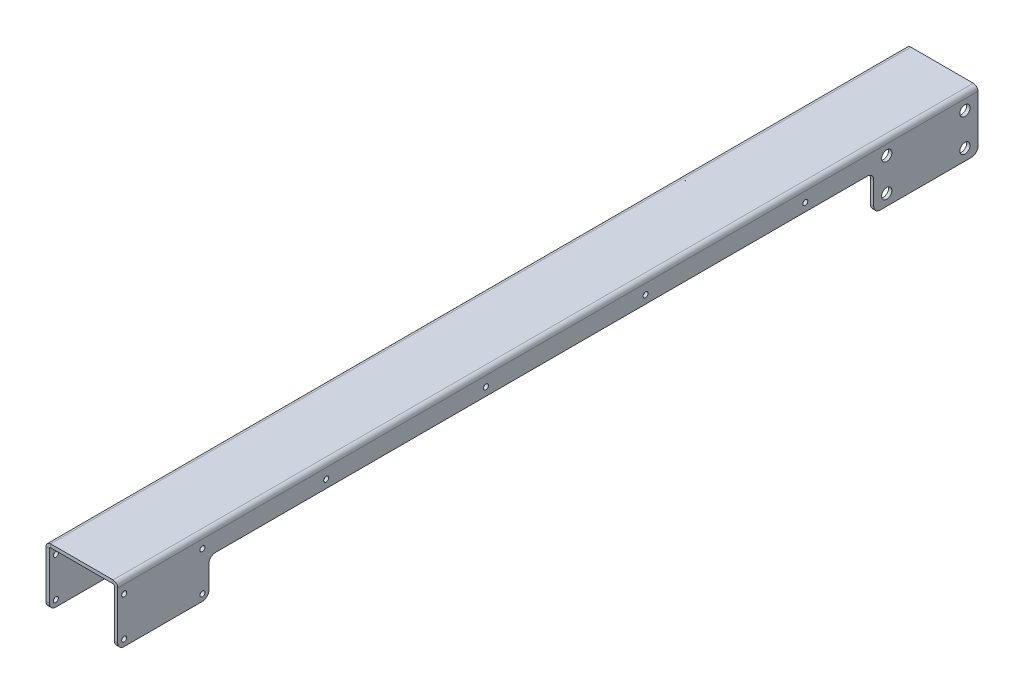
SolidWorks part; units mm, degrees
note: The reader was unsure of these and kept them because the rebuilt part matched: flange length of "Edge-Flange2".
material "5052-H32"
ref_plane "Front Plane" through (0, 0, 0) normal (0, 0, 1) x (1, 0, 0)
ref_plane "Top Plane" through (0, 0, 0) normal (0, 1, 0) x (1, 0, 0)
ref_plane "Right Plane" through (0, 0, 0) normal (1, 0, 0) x (0, 0, -1)
sketch "Sketch1" plane through (0, 0, 0) normal (0, 1, 0) x (1, 0, 0)
  line L1 (-34.925, 838.2) -> (34.925, 838.2)
  line L2 (-34.925, 838.2) -> (-34.925, 0)
  line L3 (-34.925, 0) -> (34.925, 0)
  line L4 (34.925, 838.2) -> (34.925, 0)
  point P4 (0, 0)
  dimension "D1" = 69.85
  dimension "D2" = 838.2
base flange "Base-Flange1" sketch "Sketch1" thickness 3.2639 reverse thickness direction no parameters "D1"=1.27
edge flange "Edge-Flange2" sketch "Sketch21" flange profiles "Sketch21", "Sketch22" flange angle 90 flange length 22.225 flange position material inside bend radius 1.27 thickness 3.2639 relief rectangular parameters "D6"=10, "D8"=1
sketch "Sketch21" plane through (34.925, -3.2639, 0) normal (-1, 0, 0) x (0, 0, -1)
  line L2 (0, 0) -> (0, 18.9611)
  line L3 (0, 18.9611) -> (838.2, 18.9611)
  line L4 (838.2, 18.9611) -> (838.2, 0)
  line L5 (838.2, 0) -> (0, 0) construction
  line L6 (838.2, 0) -> (0, 0)
sketch "Sketch22" plane through (-34.925, -3.2639, 0) normal (1, 0, 0) x (0, 0, 1)
  line L0 (0, 0) -> (-838.2, 0) construction
  line L1 (0, 0) -> (-838.2, 0)
  line L2 (0, 0) -> (0, 18.9611)
  line L3 (0, 18.9611) -> (-838.2, 18.9611)
  line L4 (-838.2, 18.9611) -> (-838.2, 0)
bend "EdgeBend2" bend radius 1.27 bend angle 90 parameters "D5"=1
bend "EdgeBend3" bend radius 1.27 bend angle 90 parameters "D5"=2
sketch "Sketch23" plane through (-34.925, 0, 0) normal (-1, 0, 0) x (0, 0, 1)
  line L0 (-838.2, 0) -> (0, 0) construction
  line L1 (-838.2, -22.225) -> (-736.6, -22.225)
  line L2 (-838.2, -22.225) -> (-838.2, -57.15)
  line L3 (-838.2, -57.15) -> (-736.6, -57.15)
  line L4 (-736.6, -22.225) -> (-736.6, -57.15)
  dimension "D1" = 101.6
  dimension "D2" = 57.15
extrude "Boss-Extrude1" add sketch "Sketch23" against normal up to surface (3.2639 mm away) up to face at (-31.6611, -13.3794, -419.1)
sketch "Sketch24" plane through (34.925, 0, 0) normal (1, 0, 0) x (0, 0, -1)
  line L4 (838.2, -22.225) -> (736.6, -22.225)
  line L5 (736.6, -22.225) -> (736.6, -57.15)
  line L6 (736.6, -57.15) -> (838.2, -57.15)
  line L7 (838.2, -57.15) -> (838.2, -22.225)
  line L8 (838.2, -22.225) -> (736.6, -22.225)
  line L9 (736.6, -22.225) -> (736.6, -57.15)
  line L10 (736.6, -57.15) -> (838.2, -57.15)
  line L11 (838.2, -57.15) -> (838.2, -22.225)
  dimension "D1" = 0
extrude "Boss-Extrude2" add sketch "Sketch24" against normal up to surface (3.2639 mm away) up to face at (31.6611, -13.3794, -419.1)
sketch "Sketch32" plane through (-34.925, 0, 0) normal (-1, 0, 0) x (0, 0, 1)
  line L0 (-838.2, -57.15) -> (-736.6, -57.15) construction
  line L1 (0, -22.225) -> (-88.9, -22.225)
  line L2 (0, -22.225) -> (0, -57.15)
  line L3 (0, -57.15) -> (-88.9, -57.15)
  line L4 (-88.9, -22.225) -> (-88.9, -57.15)
  dimension "D1" = 88.9
extrude "Boss-Extrude3" add sketch "Sketch32" against normal up to surface (3.2639 mm away)
sketch "Sketch33" plane through (34.925, 0, 0) normal (1, 0, 0) x (0, 0, -1)
  line L4 (88.9, -22.225) -> (0, -22.225)
  line L5 (88.9, -57.15) -> (88.9, -22.225)
  line L6 (0, -57.15) -> (88.9, -57.15)
  line L7 (0, -22.225) -> (0, -57.15)
  line L8 (88.9, -22.225) -> (0, -22.225)
  line L9 (88.9, -57.15) -> (88.9, -22.225)
  line L10 (0, -57.15) -> (88.9, -57.15)
  line L11 (0, -22.225) -> (0, -57.15)
  dimension "D1" = 0
extrude "Boss-Extrude4" add sketch "Sketch33" against normal up to surface (3.2639 mm away)
sketch "Sketch25" plane through (-34.925, 0, 0) normal (-1, 0, 0) x (0, 0, 1)
  line L0 (-838.2, 0) -> (0, 0) construction
  line L1 (0, -4.5339) -> (0, -57.15) construction
  point P0 (-203.2, -14.2875)
  dimension "D1" = 14.2875
  dimension "D2" = 203.2
hole_wizard "#10 (0.1935) Diameter Hole2" positions "Sketch26" profile "Sketch27" hole size "#10" standard "ANSI Inch" end condition through all
sketch "Sketch26" plane through (-34.925, 0, 0) normal (-1, 0, 0) x (0, 0, 1)
  point P0 (-203.2, -14.2875)
sketch "Sketch27" plane through (-34.925, -14.2875, -203.2) normal (0, 1, 0) x (0, 0, 1)
  line L0 (0, 0) -> (0, 69.85)
  line L1 (0, 69.85) -> (2.4574, 69.85)
  line L2 (2.4574, 69.85) -> (2.4574, 0)
  line L5 (2.4574, 0) -> (0, 0)
  line L11 (0, -6.35) -> (0, 107.95) construction
  dimension "Thru Hole Dia." = 4.9149
  dimension "Thru Hole Depth" = 69.85
pattern_linear "LPattern2" count 4 spacing 155.575 along (0, 0, -1) of "#10 (0.1935) Diameter Hole2"
sketch "Sketch29" plane through (-34.925, 0, 0) normal (-1, 0, 0) x (0, 0, 1)
  line L1 (-825.5, -14.4429) -> (-749.3, -14.4429)
  line L2 (-825.5, -14.4429) -> (-825.5, -46.1929)
  line L3 (-825.5, -46.1929) -> (-749.3, -46.1929)
  line L4 (-749.3, -14.4429) -> (-749.3, -46.1929)
  line L5 (0, -4.5339) -> (0, -57.15) construction
  line L6 (-838.2, -57.15) -> (-736.6, -57.15) construction
  dimension "D1" = 76.2
  dimension "D2" = 31.75
  dimension "D3" = 42.7071
  dimension "D4" = 749.3
hole_wizard "25/64 (0.39063) Diameter Hole1" positions "Sketch30" profile "Sketch31" hole size "25/64" standard "ANSI Inch" end condition through all
sketch "Sketch30" plane through (-34.925, 0, 0) normal (-1, 0, 0) x (0, 0, 1)
  point P0 (-825.5, -14.4429)
  point P3 (-825.5, -46.1929)
  point P6 (-749.3, -14.4429)
  point P9 (-749.3, -46.1929)
sketch "Sketch31" plane through (-34.925, -14.4429, -825.5) normal (0, 1, 0) x (0, 0, 1)
  line L0 (0, 0) -> (0, 69.85)
  line L1 (0, 69.85) -> (4.961, 69.85)
  line L2 (4.961, 69.85) -> (4.961, 0)
  line L5 (4.961, 0) -> (0, 0)
  line L11 (0, -6.35) -> (0, 107.95) construction
  dimension "Thru Hole Dia." = 9.922
  dimension "Thru Hole Depth" = 69.85
sketch "Sketch34" plane through (-34.925, 0, 0) normal (-1, 0, 0) x (0, 0, 1)
  line L0 (0, -4.5339) -> (0, -57.15) construction
  line L1 (-6.35, -12.7) -> (-82.55, -12.7)
  line L2 (-6.35, -12.7) -> (-6.35, -50.8)
  line L3 (-6.35, -50.8) -> (-82.55, -50.8)
  line L4 (-82.55, -12.7) -> (-82.55, -50.8)
  line L7 (-838.2, 0) -> (0, 0) construction
  dimension "D1" = 76.2
  dimension "D2" = 38.1
  dimension "D3" = 6.35
  dimension "D4" = 12.7
hole_wizard "#10 (0.1935) Diameter Hole3" positions "Sketch35" profile "Sketch36" hole size "#10" standard "ANSI Inch" end condition through all
sketch "Sketch35" plane through (-34.925, 0, 0) normal (-1, 0, 0) x (0, 0, 1)
  point P0 (-82.55, -12.7)
  point P3 (-82.55, -50.8)
  point P6 (-6.35, -12.7)
  point P9 (-6.35, -50.8)
sketch "Sketch36" plane through (-34.925, -12.7, -82.55) normal (0, 1, 0) x (0, 0, 1)
  line L0 (0, 0) -> (0, 69.85)
  line L1 (0, 69.85) -> (2.4574, 69.85)
  line L2 (2.4574, 69.85) -> (2.4574, 0)
  line L5 (2.4574, 0) -> (0, 0)
  line L11 (0, -6.35) -> (0, 107.95) construction
  dimension "Thru Hole Dia." = 4.9149
  dimension "Thru Hole Depth" = 69.85
fillet "Fillet2" radius 6.35 12 edges at (-33.2931, -22.225, -736.6) (33.293, -22.225, -736.6) (33.2931, -57.15, -736.6) (-33.2931, -57.15, -736.6) (-33.2931, -57.15, -838.2) (33.293, -57.15, -838.2) (33.2931, -57.15, -88.9) (-33.2931, -57.15, -88.9) (-33.2931, -22.225, -88.9) (33.2931, -22.225, -88.9) (33.2931, -57.15, 0) (-33.2931, -57.15, 0)
sketch "Bend-Lines1" [suppressed] plane through (0, 0, 0) normal (0, 1, 0) x (1, 0, 0)
sketch "Bounding-Box1" [suppressed] plane through (0, 0, 0) normal (0, 1, 0) x (1, 0, 0)
sheet metal parameters "Sheet-Metal1" thickness 3.2639 parameters "D1"=1.27
flat pattern "Flat-Pattern1" [suppressed]
sketch "Bend-Lines2" plane through (0, 0, 0) normal (0, 1, 0) x (1, 0, 0)
sketch3d "Bounding-Box2" [suppressed]
  line L0 (-34.925, 685.8, 0) -> (-34.925, 0, 0) construction
  line L1 (34.925, 685.8, 0) -> (34.925, 0, 0) construction
  line L2 (-34.925, 685.8, 0) -> (34.925, 685.8, 0) construction
  line L3 (-34.925, 0, 0) -> (34.925, 0, 0) construction
sketch "Sketch12-2" [suppressed] plane through (0, -3.2639, 0) normal (0, -1, 0) x (1, 0, 0)
  line L0 (-34.925, -866.8593) -> (34.925, -866.8593)
  line L1 (34.925, -685.8) -> (-34.925, -685.8) construction
  dimension "D1" = 181.0593
  dimension "D2" = 69.85
sheet metal parameters "Sheet-Metal20" thickness 3.2639 parameters "D1"=1.27
flat pattern "Flat-Pattern1"
sketch "Bend-Lines2" plane through (0, 0, 0) normal (0, 1, 0) x (1, 0, 0)
  line L0 (-32.6703, 863.6) -> (-32.6703, 0) construction
  line L1 (32.6703, 0) -> (32.6703, 863.6) construction
  line L2 (-32.6703, 863.6) -> (-32.6703, 0) construction
  line L3 (32.6703, 0) -> (32.6703, 863.6) construction
sketch3d "Bounding-Box2" [suppressed]
  line L0 (-52.6406, 863.6, 0) -> (-52.6406, 0, 0) construction
  line L1 (52.6406, 863.6, 0) -> (52.6406, 0, 0) construction
  line L2 (-52.6406, 863.6, 0) -> (52.6406, 863.6, 0) construction
  line L3 (-52.6406, 0, 0) -> (52.6406, 0, 0) construction
bend of the flat pattern "Flatten-<EdgeBend2>1"
bend of the flat pattern "Flatten-<EdgeBend3>1"
sheet metal parameters "Sheet-Metal21" thickness 3.2639 parameters "D1"=1.27
flat pattern "Flat-Pattern1"
sketch "Bend-Lines2" plane through (0, 0, 0) normal (0, 1, 0) x (1, 0, 0)
  line L0 (-32.6703, 863.6) -> (-32.6703, 0) construction
  line L1 (32.6703, 0) -> (32.6703, 863.6) construction
  line L2 (-32.6703, 863.6) -> (-32.6703, 0) construction
  line L3 (32.6703, 0) -> (32.6703, 863.6) construction
sketch3d "Bounding-Box2" [suppressed]
  line L0 (-93.9156, 863.6, 0) -> (-93.9156, 0, 0) construction
  line L1 (52.6406, 863.6, 0) -> (52.6406, 0, 0) construction
  line L2 (-93.9156, 863.6, 0) -> (52.6406, 863.6, 0) construction
  line L3 (-93.9156, 0, 0) -> (52.6406, 0, 0) construction
bend of the flat pattern "Flatten-<EdgeBend2>1"
bend of the flat pattern "Flatten-<EdgeBend3>1"
sheet metal parameters "Sheet-Metal22" thickness 3.2639 parameters "D1"=1.27
flat pattern "Flat-Pattern1"
sketch "Bend-Lines2" plane through (0, 0, 0) normal (0, 1, 0) x (1, 0, 0)
  line L0 (-32.6703, 863.6) -> (-32.6703, 0) construction
  line L1 (32.6703, 0) -> (32.6703, 863.6) construction
  line L2 (-32.6703, 863.6) -> (-32.6703, 0) construction
  line L3 (32.6703, 0) -> (32.6703, 863.6) construction
sketch3d "Bounding-Box2" [suppressed]
  line L0 (-93.9156, 863.6, 0) -> (-93.9156, 0, 0) construction
  line L1 (93.9156, 863.6, 0) -> (93.9156, 0, 0) construction
  line L2 (-93.9156, 863.6, 0) -> (93.9156, 863.6, 0) construction
  line L3 (-93.9156, 0, 0) -> (93.9156, 0, 0) construction
bend of the flat pattern "Flatten-<EdgeBend2>1"
bend of the flat pattern "Flatten-<EdgeBend3>1"
sheet metal parameters "Sheet-Metal23" thickness 3.2639 parameters "D1"=1.27
flat pattern "Flat-Pattern1" [suppressed]
sketch "Bend-Lines2" plane through (0, 0, 0) normal (0, 1, 0) x (1, 0, 0)
  line L0 (-32.6703, 863.6) -> (-32.6703, 0) construction
  line L1 (32.6703, 0) -> (32.6703, 863.6) construction
  line L2 (-32.6703, 863.6) -> (-32.6703, 0) construction
  line L3 (32.6703, 0) -> (32.6703, 863.6) construction
sketch3d "Bounding-Box2" [suppressed]
  line L0 (-93.9156, 863.6, 0) -> (-93.9156, 0, 0) construction
  line L1 (93.9156, 863.6, 0) -> (93.9156, 0, 0) construction
  line L2 (-93.9156, 863.6, 0) -> (93.9156, 863.6, 0) construction
  line L3 (-93.9156, 0, 0) -> (93.9156, 0, 0) construction
bend of the flat pattern "Flatten-<EdgeBend2>1"
bend of the flat pattern "Flatten-<EdgeBend3>1"
sketch "Sketch25-1" [suppressed] plane through (-30.4156, 0, 0) normal (0, 1, 0) x (0, 0, 1)
  line L0 (-863.6, 0) -> (0, 0) construction
  line L1 (0, 83.0561) -> (0, -22.225) construction
  point P0 (-12.7, -14.2875)
  dimension "D1" = 14.2875
  dimension "D2" = 12.7
sheet metal parameters "Sheet-Metal24" thickness 3.2639 parameters "D1"=1.27
flat pattern "Flat-Pattern1" [suppressed]
sketch "Bend-Lines2" plane through (0, 0, 0) normal (0, 1, 0) x (1, 0, 0)
  line L0 (-32.6703, 838.2) -> (-32.6703, 0) construction
  line L1 (32.6703, 0) -> (32.6703, 838.2) construction
  line L2 (-32.6703, 838.2) -> (-32.6703, 0) construction
  line L3 (32.6703, 0) -> (32.6703, 838.2) construction
sketch3d "Bounding-Box2" [suppressed]
  line L0 (-93.9156, 838.2, 0) -> (-93.9156, 0, 0) construction
  line L1 (93.9156, 838.2, 0) -> (93.9156, 0, 0) construction
  line L2 (-93.9156, 838.2, 0) -> (93.9156, 838.2, 0) construction
  line L3 (-93.9156, 0, 0) -> (93.9156, 0, 0) construction
bend of the flat pattern "Flatten-<EdgeBend2>1"
bend of the flat pattern "Flatten-<EdgeBend3>1"
sketch "Sketch25-1" [suppressed] plane through (-30.4156, 0, 0) normal (0, 1, 0) x (0, 0, 1)
  line L0 (-838.2, 0) -> (0, 0) construction
  line L1 (0, 83.0561) -> (0, -22.225) construction
  point P0 (-12.7, -14.2875)
  dimension "D1" = 14.2875
  dimension "D2" = 12.7
sheet metal parameters "Sheet-Metal25" thickness 3.2639 parameters "D1"=1.27
flat pattern "Flat-Pattern1" [suppressed]
sketch "Bend-Lines2" plane through (0, 0, 0) normal (0, 1, 0) x (1, 0, 0)
  line L0 (-32.6703, 838.2) -> (-32.6703, 0) construction
  line L1 (32.6703, 0) -> (32.6703, 838.2) construction
  line L2 (-32.6703, 838.2) -> (-32.6703, 0) construction
  line L3 (32.6703, 0) -> (32.6703, 838.2) construction
sketch3d "Bounding-Box2" [suppressed]
  line L0 (-87.5656, 838.2, 0) -> (-87.5656, 0, 0) construction
  line L1 (87.5656, 838.2, 0) -> (87.5656, 0, 0) construction
  line L2 (-87.5656, 838.2, 0) -> (87.5656, 838.2, 0) construction
  line L3 (-87.5656, 0, 0) -> (87.5656, 0, 0) construction
bend of the flat pattern "Flatten-<EdgeBend2>1"
bend of the flat pattern "Flatten-<EdgeBend3>1"
sketch "Sketch25-1" [suppressed] plane through (-30.4156, 0, 0) normal (0, 1, 0) x (0, 0, 1)
  line L0 (-838.2, 0) -> (0, 0) construction
  line L1 (0, 117.9811) -> (0, -57.15) construction
  point P0 (-203.2, -14.2875)
  dimension "D1" = 14.2875
  dimension "D2" = 203.2
sketch "Sketch29-1" [suppressed] plane through (-30.4156, 0, 0) normal (0, 1, 0) x (0, 0, 1)
  line L1 (-825.5, -14.4429) -> (-749.3, -14.4429)
  line L2 (-825.5, -14.4429) -> (-825.5, -46.1929)
  line L3 (-825.5, -46.1929) -> (-749.3, -46.1929)
  line L4 (-749.3, -14.4429) -> (-749.3, -46.1929)
  line L5 (0, 117.9811) -> (0, -57.15) construction
  line L6 (-838.2, -57.15) -> (-736.6, -57.15) construction
  dimension "D1" = 76.2
  dimension "D2" = 31.75
  dimension "D3" = 42.7071
  dimension "D4" = 749.3
sheet metal parameters "Sheet-Metal26" thickness 3.2639 parameters "D1"=1.27
flat pattern "Flat-Pattern1" [suppressed]
sketch "Bend-Lines2" plane through (0, 0, 0) normal (0, 1, 0) x (1, 0, 0)
  line L0 (-32.6703, 838.2) -> (-32.6703, 0) construction
  line L1 (32.6703, 0) -> (32.6703, 838.2) construction
  line L2 (-32.6703, 838.2) -> (-32.6703, 0) construction
  line L3 (32.6703, 0) -> (32.6703, 838.2) construction
sketch3d "Bounding-Box2" [suppressed]
  line L0 (-87.5656, 838.2, 0) -> (-87.5656, 0, 0) construction
  line L1 (87.5656, 838.2, 0) -> (87.5656, 0, 0) construction
  line L2 (-87.5656, 838.2, 0) -> (87.5656, 838.2, 0) construction
  line L3 (-87.5656, 0, 0) -> (87.5656, 0, 0) construction
bend of the flat pattern "Flatten-<EdgeBend2>1"
bend of the flat pattern "Flatten-<EdgeBend3>1"
sketch "Sketch25-1" [suppressed] plane through (-30.4156, 0, 0) normal (0, 1, 0) x (0, 0, 1)
  line L0 (-838.2, 0) -> (0, 0) construction
  line L1 (0, 83.0561) -> (0, -57.15) construction
  point P0 (-12.7, -14.2875)
  dimension "D1" = 14.2875
  dimension "D2" = 12.7
sketch "Sketch29-1" [suppressed] plane through (-30.4156, 0, 0) normal (0, 1, 0) x (0, 0, 1)
  line L1 (-825.5, -11.2679) -> (-749.3, -11.2679)
  line L2 (-825.5, -11.2679) -> (-825.5, -43.0179)
  line L3 (-825.5, -43.0179) -> (-749.3, -43.0179)
  line L4 (-749.3, -11.2679) -> (-749.3, -43.0179)
  line L5 (0, 83.0561) -> (0, -57.15) construction
  line L6 (-838.2, -57.15) -> (-736.6, -57.15) construction
  dimension "D1" = 76.2
  dimension "D2" = 31.75
  dimension "D3" = 45.8821
  dimension "D4" = 749.3
sheet metal parameters "Sheet-Metal27" thickness 3.2639 parameters "D1"=1.27
flat pattern "Flat-Pattern1" [suppressed]
sketch "Bend-Lines2" plane through (0, 0, 0) normal (0, 1, 0) x (1, 0, 0)
  line L0 (-32.6703, 838.2) -> (-32.6703, 0) construction
  line L1 (32.6703, 0) -> (32.6703, 838.2) construction
  line L2 (-32.6703, 838.2) -> (-32.6703, 0) construction
  line L3 (32.6703, 0) -> (32.6703, 838.2) construction
sketch3d "Bounding-Box2" [suppressed]
  line L0 (-87.5656, 838.2, 0) -> (-87.5656, 0, 0) construction
  line L1 (87.5656, 838.2, 0) -> (87.5656, 0, 0) construction
  line L2 (-87.5656, 838.2, 0) -> (87.5656, 838.2, 0) construction
  line L3 (-87.5656, 0, 0) -> (87.5656, 0, 0) construction
bend of the flat pattern "Flatten-<EdgeBend2>1"
bend of the flat pattern "Flatten-<EdgeBend3>1"
sketch "Sketch25-1" [suppressed] plane through (-30.4156, 0, 0) normal (0, 1, 0) x (0, 0, 1)
  line L0 (-838.2, 0) -> (0, 0) construction
  line L1 (0, 117.9811) -> (0, -57.15) construction
  point P0 (-12.7, -14.2875)
  dimension "D1" = 14.2875
  dimension "D2" = 12.7
sketch "Sketch29-1" [suppressed] plane through (-30.4156, 0, 0) normal (0, 1, 0) x (0, 0, 1)
  line L1 (-825.5, -11.2679) -> (-749.3, -11.2679)
  line L2 (-825.5, -11.2679) -> (-825.5, -43.0179)
  line L3 (-825.5, -43.0179) -> (-749.3, -43.0179)
  line L4 (-749.3, -11.2679) -> (-749.3, -43.0179)
  line L5 (0, 117.9811) -> (0, -57.15) construction
  line L6 (-838.2, -57.15) -> (-736.6, -57.15) construction
  dimension "D1" = 76.2
  dimension "D2" = 31.75
  dimension "D3" = 45.8821
  dimension "D4" = 749.3
sheet metal parameters "Sheet-Metal28" thickness 3.2639 parameters "D1"=1.27
flat pattern "Flat-Pattern1" [suppressed]
sketch "Bend-Lines2" plane through (0, 0, 0) normal (0, 1, 0) x (1, 0, 0)
  line L0 (-32.6703, 838.2) -> (-32.6703, 0) construction
  line L1 (32.6703, 0) -> (32.6703, 838.2) construction
  line L2 (-32.6703, 838.2) -> (-32.6703, 0) construction
  line L3 (32.6703, 0) -> (32.6703, 838.2) construction
sketch3d "Bounding-Box2" [suppressed]
  line L0 (87.5656, 838.2, 0) -> (87.5656, 0, 0) construction
  line L1 (-87.5655, 838.2, 0) -> (-87.5656, 0, 0) construction
  line L2 (87.5656, 838.2, 0) -> (-87.5655, 838.2, 0) construction
  line L3 (87.5656, 0, 0) -> (-87.5656, 0, 0) construction
bend of the flat pattern "Flatten-<EdgeBend2>1"
bend of the flat pattern "Flatten-<EdgeBend3>1"
sketch "Sketch25-1" [suppressed] plane through (-30.4156, 0, 0) normal (0, 1, 0) x (0, 0, 1)
  line L0 (-838.2, 0) -> (0, 0) construction
  line L1 (0, 111.6311) -> (0, -50.8) construction
  point P0 (-203.2, -14.2875)
  dimension "D1" = 14.2875
  dimension "D2" = 203.2
sketch "Sketch29-1" [suppressed] plane through (-30.4156, 0, 0) normal (0, 1, 0) x (0, 0, 1)
  line L1 (-825.5, -14.4429) -> (-749.3, -14.4429)
  line L2 (-825.5, -14.4429) -> (-825.5, -46.1929)
  line L3 (-825.5, -46.1929) -> (-749.3, -46.1929)
  line L4 (-749.3, -14.4429) -> (-749.3, -46.1929)
  line L5 (0, 111.6311) -> (0, -50.8) construction
  line L6 (-831.85, -57.15) -> (-742.95, -57.15) construction
  dimension "D1" = 76.2
  dimension "D2" = 31.75
  dimension "D3" = 42.7071
  dimension "D4" = 749.3
sketch "Sketch34-1" [suppressed] plane through (-30.4156, 0, 0) normal (0, 1, 0) x (0, 0, 1)
  line L0 (0, 111.6311) -> (0, -50.8) construction
  line L1 (-6.35, -12.7) -> (-82.55, -12.7)
  line L2 (-6.35, -12.7) -> (-6.35, -50.8)
  line L3 (-6.35, -50.8) -> (-82.55, -50.8)
  line L4 (-82.55, -12.7) -> (-82.55, -50.8)
  line L7 (-838.2, 0) -> (0, 0) construction
  dimension "D1" = 76.2
  dimension "D2" = 38.1
  dimension "D3" = 6.35
  dimension "D4" = 12.7
